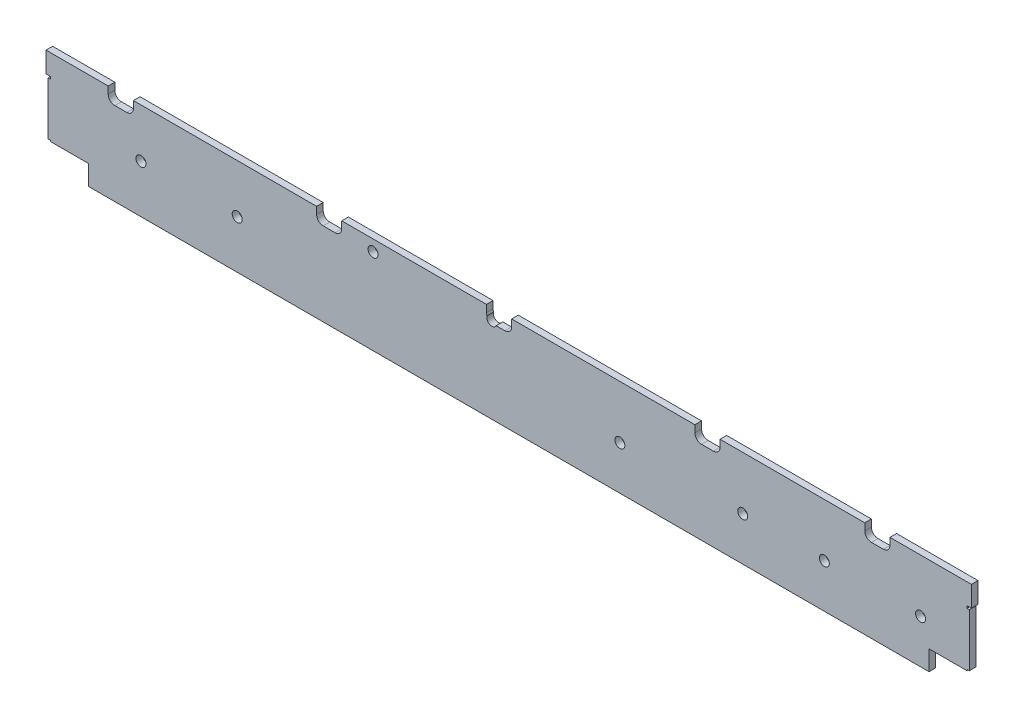
SolidWorks part; units mm, degrees
material "PP Film"
ref_plane "X-Y Datum" through (0, 0, 0) normal (0, 0, 1) x (1, 0, 0)
ref_plane "X-Z Datum" through (0, 0, 0) normal (0, 1, 0) x (1, 0, 0)
ref_plane "Y-Z Datum" through (0, 0, 0) normal (1, 0, 0) x (0, 0, -1)
sketch "Sketch2" plane through (0, 0, 0) normal (0, 0, 1) x (1, 0, 0)
  line L0 (-174.4992, -157.216) -> (269.7668, -157.216)
  line L20 (249.4468, -203.714) -> (249.4468, -194.181)
  line L21 (249.4468, -194.181) -> (267.6238, -194.181)
  line L22 (267.6238, -194.181) -> (267.6238, -193.665)
  line L23 (267.6238, -193.665) -> (268.7668, -193.665)
  line L24 (268.7668, -193.665) -> (268.7668, -168.265)
  line L25 (268.7668, -168.265) -> (267.6238, -168.265)
  line L26 (267.6238, -168.265) -> (267.6238, -167.122)
  line L27 (267.6238, -167.122) -> (269.7668, -167.122)
  line L28 (269.7668, -167.122) -> (269.7668, -157.216)
  line L29 (269.7668, -157.216) -> (230.6663, -157.216)
  line L30 (-174.4992, -157.216) -> (-174.4992, -167.122)
  line L31 (-174.4992, -167.122) -> (-172.3562, -167.122)
  line L32 (-172.3562, -167.122) -> (-172.3562, -168.265)
  line L33 (-172.3562, -168.265) -> (-173.4992, -168.265)
  line L34 (-173.4992, -168.265) -> (-173.4992, -193.665)
  line L35 (-173.4992, -193.665) -> (-172.3562, -193.665)
  line L36 (-172.3562, -193.665) -> (-172.3562, -194.181)
  line L37 (-172.3562, -194.181) -> (-154.1792, -194.181)
  line L38 (-154.1792, -194.181) -> (-154.1792, -203.714)
  line L39 (-154.1792, -203.714) -> (249.4468, -203.714)
  line L41 (249.4468, -194.181) -> (267.6238, -194.181)
  line L42 (267.6238, -194.181) -> (267.6238, -193.665)
  line L43 (267.6238, -193.665) -> (268.7668, -193.665)
  line L44 (268.7668, -193.665) -> (268.7668, -168.265)
  line L45 (268.7668, -168.265) -> (267.6238, -168.265)
  line L46 (267.6238, -168.265) -> (267.6238, -167.122)
  line L47 (267.6238, -167.122) -> (269.7668, -167.122)
  line L48 (269.7668, -167.122) -> (269.7668, -157.216)
  line L50 (-174.4992, -157.216) -> (-174.4992, -167.122)
  line L51 (-174.4992, -167.122) -> (-172.3562, -167.122)
  line L52 (-172.3562, -167.122) -> (-172.3562, -168.265)
  line L53 (-172.3562, -168.265) -> (-173.4992, -168.265)
  line L54 (-173.4992, -168.265) -> (-173.4992, -193.665)
  line L55 (-173.4992, -193.665) -> (-172.3562, -193.665)
  line L56 (-172.3562, -193.665) -> (-172.3562, -194.181)
  line L57 (-172.3562, -194.181) -> (-154.1792, -194.181)
  line L58 (-154.1792, -194.181) -> (-154.1792, -203.714)
  line L59 (-154.1792, -203.714) -> (249.4468, -203.714)
  line L196 (249.4468, -203.714) -> (249.4468, -194.181)
  line L231 (227.4913, -163.756) -> (221.7613, -163.756)
  line L233 (227.4913, -163.756) -> (221.7613, -163.756)
  line L235 (218.5863, -160.581) -> (218.5863, -157.216)
  line L237 (218.5863, -160.581) -> (218.5863, -157.216)
  line L239 (218.5863, -157.216) -> (149.0973, -157.216)
  line L241 (218.5863, -157.216) -> (149.0973, -157.216)
  line L243 (149.0973, -157.216) -> (149.0973, -160.581)
  line L245 (149.0973, -157.216) -> (149.0973, -160.581)
  line L247 (145.9223, -163.756) -> (140.1923, -163.756)
  line L249 (145.9223, -163.756) -> (140.1923, -163.756)
  line L259 (137.0173, -160.581) -> (137.0173, -157.216)
  line L263 (137.0173, -160.581) -> (137.0173, -157.216)
  line L267 (137.0173, -157.216) -> (49.0523, -157.216)
  line L271 (137.0173, -157.216) -> (49.0523, -157.216)
  line L275 (49.0523, -157.216) -> (49.0523, -160.581)
  line L279 (49.0523, -157.216) -> (49.0523, -160.581)
  line L283 (45.8773, -163.756) -> (40.1473, -163.756)
  line L287 (45.8773, -163.756) -> (40.1473, -163.756)
  line L291 (36.9723, -160.581) -> (36.9723, -157.216)
  line L295 (36.9723, -160.581) -> (36.9723, -157.216)
  line L369 (36.9723, -157.216) -> (-32.5167, -157.216)
  line L370 (36.9723, -157.216) -> (-32.5167, -157.216)
  line L371 (-32.5167, -157.216) -> (-32.5167, -160.581)
  line L372 (-32.5167, -157.216) -> (-32.5167, -160.581)
  line L373 (-35.6917, -163.756) -> (-41.4217, -163.756)
  line L374 (-35.6917, -163.756) -> (-41.4217, -163.756)
  line L375 (-44.5967, -160.581) -> (-44.5967, -157.216)
  line L376 (-44.5967, -160.581) -> (-44.5967, -157.216)
  line L377 (-44.5967, -157.216) -> (-132.5617, -157.216)
  line L378 (-44.5967, -157.216) -> (-132.5617, -157.216)
  line L379 (-132.5617, -157.216) -> (-132.5617, -160.581)
  line L380 (-132.5617, -157.216) -> (-132.5617, -160.581)
  line L381 (-135.7367, -163.756) -> (-141.4667, -163.756)
  line L382 (-135.7367, -163.756) -> (-141.4667, -163.756)
  line L383 (-144.6417, -160.581) -> (-144.6417, -157.216)
  line L384 (-144.6417, -160.581) -> (-144.6417, -157.216)
  line L385 (230.6663, -157.216) -> (230.6663, -160.581)
  line L386 (230.6663, -157.216) -> (230.6663, -160.581)
  line L611 (-144.6417, -157.216) -> (-174.4992, -157.216)
  arc A40 (218.5863, -160.581) -> (221.7613, -163.756) centre (221.7613, -160.581) ccw
  arc A41 (218.5863, -160.581) -> (221.7613, -163.756) centre (221.7613, -160.581) ccw
  arc A42 (145.9223, -163.756) -> (149.0973, -160.581) centre (145.9223, -160.581) ccw
  arc A43 (145.9223, -163.756) -> (149.0973, -160.581) centre (145.9223, -160.581) ccw
  arc A44 (137.0173, -160.581) -> (140.1923, -163.756) centre (140.1923, -160.581) ccw
  arc A45 (137.0173, -160.581) -> (140.1923, -163.756) centre (140.1923, -160.581) ccw
  arc A46 (45.8773, -163.756) -> (49.0523, -160.581) centre (45.8773, -160.581) ccw
  arc A47 (45.8773, -163.756) -> (49.0523, -160.581) centre (45.8773, -160.581) ccw
  arc A48 (36.9723, -160.581) -> (40.1473, -163.756) centre (40.1473, -160.581) ccw
  arc A49 (36.9723, -160.581) -> (40.1473, -163.756) centre (40.1473, -160.581) ccw
  arc A50 (-35.6917, -163.756) -> (-32.5167, -160.581) centre (-35.6917, -160.581) ccw
  arc A51 (-35.6917, -163.756) -> (-32.5167, -160.581) centre (-35.6917, -160.581) ccw
  arc A52 (-44.5967, -160.581) -> (-41.4217, -163.756) centre (-41.4217, -160.581) ccw
  arc A53 (-44.5967, -160.581) -> (-41.4217, -163.756) centre (-41.4217, -160.581) ccw
  arc A54 (-135.7367, -163.756) -> (-132.5617, -160.581) centre (-135.7367, -160.581) ccw
  arc A55 (-135.7367, -163.756) -> (-132.5617, -160.581) centre (-135.7367, -160.581) ccw
  arc A56 (-144.6417, -160.581) -> (-141.4667, -163.756) centre (-141.4667, -160.581) ccw
  arc A57 (-144.6417, -160.581) -> (-141.4667, -163.756) centre (-141.4667, -160.581) ccw
  arc A58 (227.4913, -163.756) -> (230.6663, -160.581) centre (227.4913, -160.581) ccw
  arc A59 (227.4913, -163.756) -> (230.6663, -160.581) centre (227.4913, -160.581) ccw
  dimension "D1" = 0
extrude "Boss-Extrude1" add sketch "Sketch2" along normal blind 3.175 contours L58 L59 L196 L41 L42 L43 L44 L45 L46 L47 L48 L50 L51 L52 L53 L54 L55 L56 L57 region at (47.6513, -180.4833, 0)
sketch "Sketch3" plane through (0, 0, 0) normal (0, 0, -1) x (-1, 0, 0)
  circle A0 centre (-245.3703, -182.706) radius 2
  circle A1 centre (-199.1703, -182.706) radius 2
  circle A2 centre (-159.9918, -182.714) radius 2
  circle A3 centre (-100.9918, -182.714) radius 2
  circle A4 centre (-39.5223, -162.606) radius 2
  circle A5 centre (17.4777, -162.606) radius 2
  circle A6 centre (82.7027, -180.606) radius 2
  circle A7 centre (128.9027, -180.606) radius 2
  point P0 (17.4777, -162.606)
  point P2 (-39.5223, -162.606)
  point P4 (128.9027, -180.606)
  point P6 (82.7027, -180.606)
  point P8 (-100.9918, -182.714)
  point P10 (-245.3703, -182.706)
  point P12 (-199.1703, -182.706)
  point P14 (-159.9918, -182.714)
  dimension "D1" = 4
extrude "Cut-Extrude1" cut sketch "Sketch3" against normal through all both and the other way through all
hole_wizard "M4 Clearance Hole1" positions "Sketch6" profile "Sketch5" hole size "M4" standard "ANSI Metric" end condition up to next
sketch "Sketch6" plane through (0, 0, 0) normal (0, 0, -1) x (-1, 0, 0)
  point P0 (-245.3703, -182.706)
  point P3 (-199.1703, -182.706)
  point P6 (-159.9918, -182.714)
  point P9 (-100.9918, -182.714)
  point P12 (-39.5223, -162.606)
  point P15 (17.4777, -162.606)
  point P18 (82.7027, -180.606)
  point P21 (128.9027, -180.606)
sketch "Sketch5" plane through (245.3703, -182.706, 0) normal (1, 0, 0) x (0, 1, 0)
  line L0 (0, 0) -> (0, 3.175)
  line L1 (0, 3.175) -> (2.4, 3.175)
  line L2 (2.4, 3.175) -> (2.4, 0)
  line L5 (2.4, 0) -> (0, 0)
  line L11 (0, -6.35) -> (0, 107.95) construction
  dimension "Thru Hole Dia." = 4.8
  dimension "Thru Hole Depth" = 3.175
